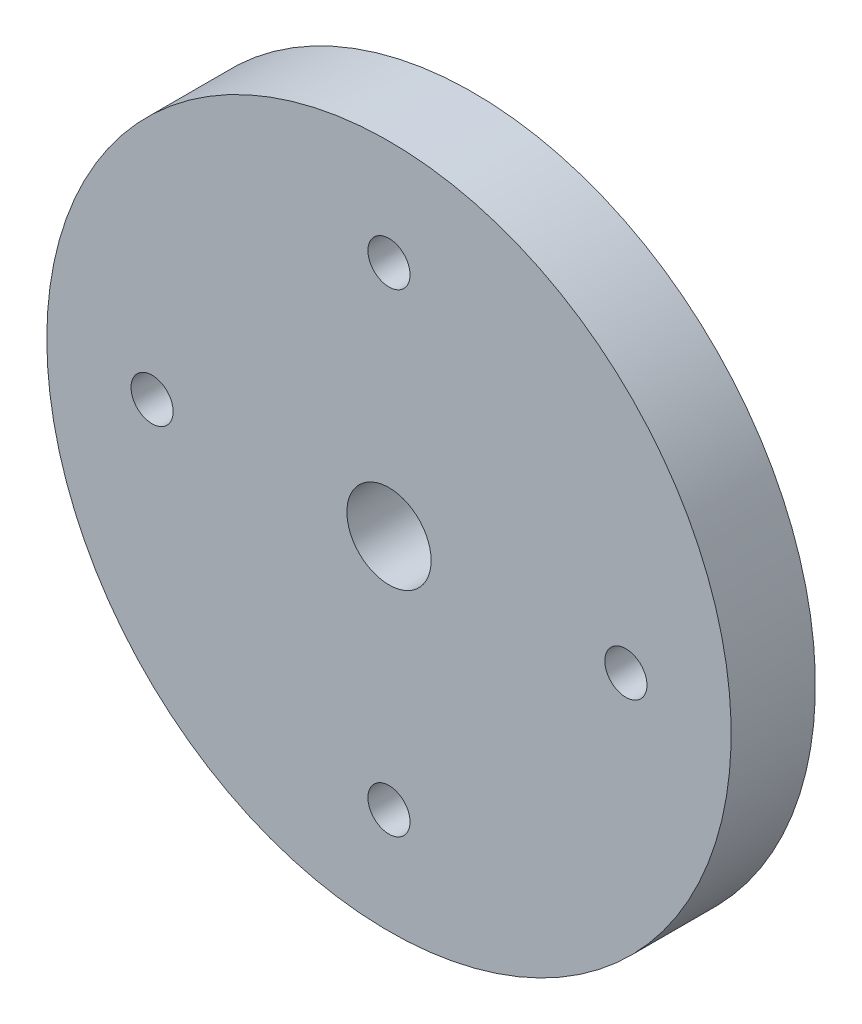
SolidWorks part; units mm, degrees
ref_plane "Ebene vorne" through (0, 0, 0) normal (0, 0, 1) x (1, 0, 0)
ref_plane "Ebene oben" through (0, 0, 0) normal (0, 1, 0) x (1, 0, 0)
ref_plane "Ebene rechts" through (0, 0, 0) normal (1, 0, 0) x (0, 0, -1)
sketch "Skizze1" plane through (0, 0, 0) normal (1, 0, 0) x (0, 0, -1)
  line L0 (0, 0) -> (0, -44862.1348) construction
  line L1 (0, 0) -> (-44862.1348, 0) construction
  line L2 (0, 0) -> (20, 0)
  line L3 (20, 0) -> (20, 15)
  line L4 (20, 15) -> (8, 15)
  line L5 (8, 15) -> (8, 32.5)
  line L6 (8, 32.5) -> (0, 32.5)
  line L7 (0, 32.5) -> (0, 0)
  dimension "D1" = 30
  dimension "D2" = 65
  dimension "D3" = 20
  dimension "D4" = 12
revolve "Rotation1" add sketch "Skizze1" angle 360 about L1
hole_wizard "Ø4.0 (4) Heat Insert M3" positions "Skizze2" profile "Skizze3" hole size "Ø4.0" standard "ISO" end condition through all
sketch "Skizze2" plane through (0, 0, 0) normal (0, 0, 1) x (1, 0, 0)
  circle A0 centre (0, 0) radius 22.5 construction
  point P7 (0, 22.5)
  point P9 (-22.5, 0)
  point P11 (0, -22.5)
  point P13 (22.5, 0)
  dimension "D1" = 45
sketch "Skizze3" plane through (22.5, 0, 0) normal (1, 0, 0) x (0, -1, 0)
  line L0 (0, 0) -> (0, 20)
  line L1 (0, 20) -> (2, 20)
  line L2 (2, 20) -> (2, 0)
  line L5 (2, 0) -> (0, 0)
  line L11 (0, -6.35) -> (0, 107.95) construction
  dimension "Bohrerdurchmesser" = 4
  dimension "Bohrungstiefe" = 20
hole_wizard "Ø8.0 (8) Durchmesser Bohrung1" positions "Skizze4" profile "Skizze5" hole size "Ø8.0" standard "ISO" end condition through all
sketch "Skizze4" plane through (0, 0, 0) normal (0, 0, 1) x (1, 0, 0)
  point P0 (0, 0)
sketch "Skizze5" plane through (0, 0, 0) normal (1, 0, 0) x (0, -1, 0)
  line L0 (0, 0) -> (0, 20)
  line L1 (0, 20) -> (4, 20)
  line L2 (4, 20) -> (4, 0)
  line L5 (4, 0) -> (0, 0)
  line L11 (0, -6.35) -> (0, 107.95) construction
  dimension "Bohrerdurchmesser" = 8
  dimension "Bohrungstiefe" = 20
sketch "Skizze8" plane through (0, 0, -20) normal (0, 0, -1) x (-1, 0, 0)
  line L0 (0, 0) -> (0, 50000) construction
  circle A0 centre (0, 0) radius 10 construction
  circle A1 centre (0, 10) radius 2
  circle A2 centre (8.6603, -5) radius 2
  circle A3 centre (-8.6603, -5) radius 2
  point P14 (0, 0)
  dimension "D1" = 20
  dimension "D2" = 4
  dimension "D3" = 3
extrude "Schnitt-Linear austragen1" cut sketch "Skizze8" against normal blind 7
